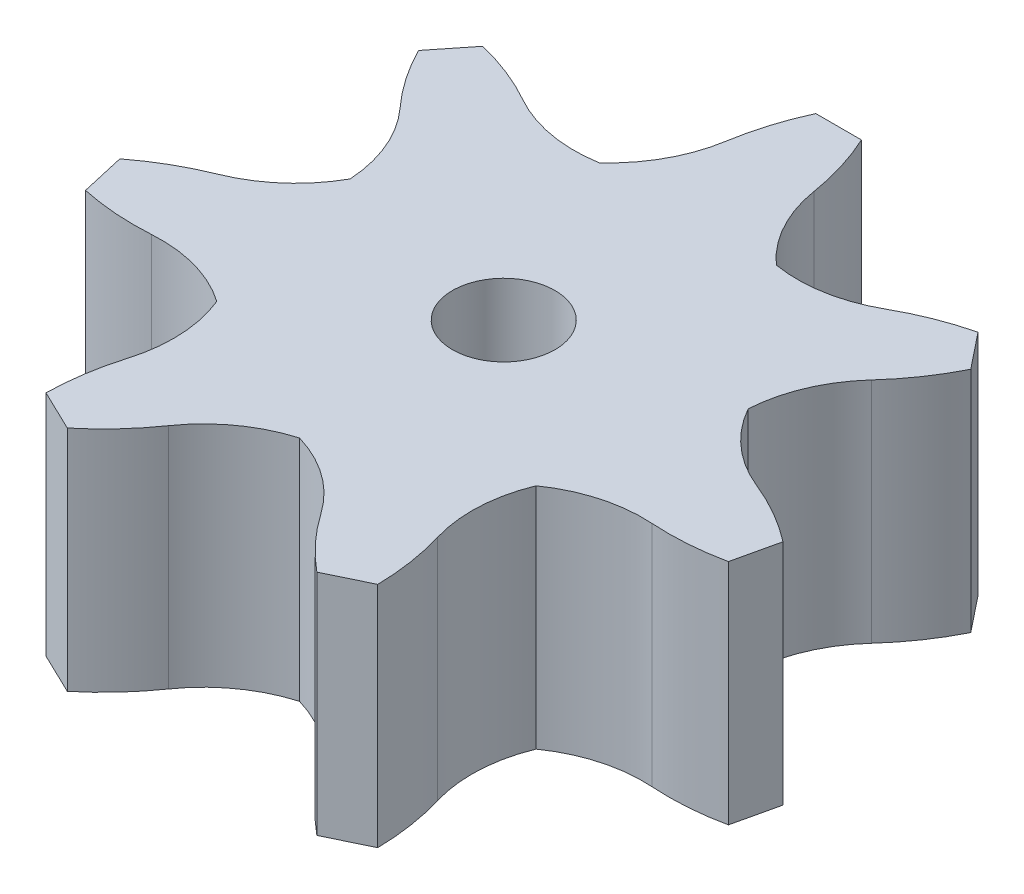
SolidWorks part; units mm, degrees
ref_plane "Front Plane" through (0, 0, 0) normal (0, 0, 1) x (1, 0, 0)
ref_plane "Top Plane" through (0, 0, 0) normal (0, 1, 0) x (1, 0, 0)
ref_plane "Right Plane" through (0, 0, 0) normal (1, 0, 0) x (0, 0, -1)
sketch "Sketch1" plane through (0, 0, 0) normal (0, 1, 0) x (1, 0, 0)
  line L2 (0.5, 7.3427) -> (-0.5, 7.3427)
  line L3 (-1, 4.3427) -> (1, 4.3427)
  line L4 (0, 7.3427) -> (0, 4.3427)
  line L6 (0, -1.125) -> (0, 1.125)
  line L8 (0, 5.8427) -> (0.9583, 5.8427)
  line L9 (0, 5.8427) -> (-0.9583, 5.8427)
  line L10 (-2, 3.9823) -> (2, 3.9823)
  circle A0 centre (0, 0) radius 4.4563
  arc A1 (-1, 4.3427) -> (-0.5, 7.3427) centre (4.6965, 4.9349) cw
  arc A2 (0.5, 7.3427) -> (1, 4.3427) centre (-4.6965, 4.9349) cw
  circle A3 centre (0, 0) radius 1.125
  arc A4 (-0.9583, 5.8427) -> (-2, 3.9823) centre (-4.0173, 6.3337) cw
  arc A5 (0.9583, 5.8427) -> (2, 3.9823) centre (4.0173, 6.3337) ccw
  dimension "D4" = 5.7272
  dimension "D5" = 8.9127
  dimension "D6" = 2.25
  dimension "D1" = 3
  dimension "D2" = 2
  dimension "D3" = 1
  dimension "D8" = 4
extrude "Boss-Extrude1" add sketch "Sketch1" along normal blind 5 contours A1 L2 A2 L3 | L10 A5 L8 L9 A4
sketch "Sketch4" plane through (0, 0, 0) normal (1, 0, 0) x (0, 0, -1)
  line L0 (0, 0) -> (0, 7.6311)
pattern_circular "CirPattern2" count 7 over 360 about axis through (0, 0, 0) along (0, 1, 0) of "Boss-Extrude1" reverse direction yes
extrude "Boss-Extrude3" add sketch "Sketch1<5>" along normal blind 5 contours L10 A0 A3 region at (3.6884, 0, -2.275)
sketch "Sketch1<5>" plane through (0, 0, 0) normal (0, 1, 0) x (1, 0, 0) same geometry as "Sketch1"
equation "\"teeth\"= 7'num of teeth in gear"
equation "\"gearRadius\"= \"teeth\" * 4 / ( 2 * Pi )"
equation "\"D5@Sketch1\"=\"gearRadius\"*2"
equation "\"D1@CirPattern2\"=\"teeth\""
equation "\"thick\"= 5"
equation "\"D1@Boss-Extrude1\"=\"thick\""
equation "\"D1@Boss-Extrude3\"=\"thick\""
equation "\"innerDia\" = 2.25"
equation "\"D6@Sketch1\"=\"innerDia\""
